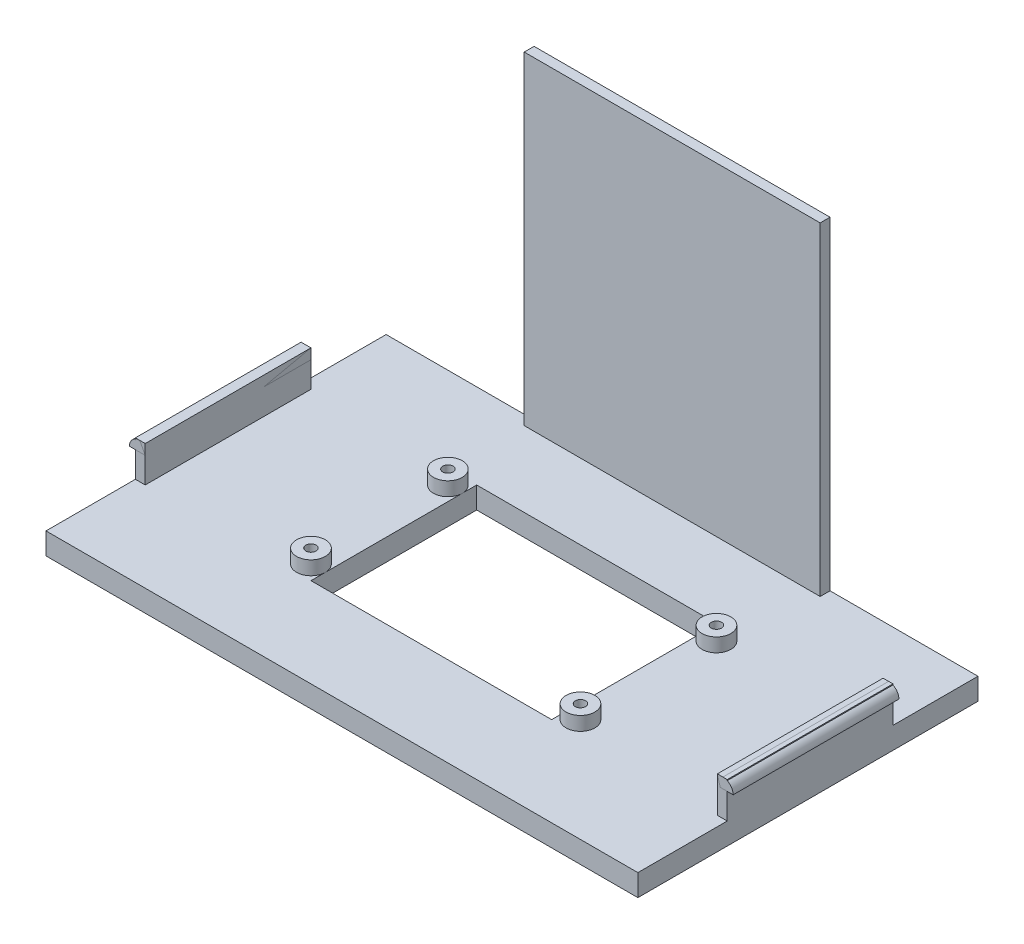
SolidWorks part; units mm, degrees
ref_plane "Plano frontal" through (0, 0, 0) normal (0, 0, 1) x (1, 0, 0)
ref_plane "Plano superior" through (0, 0, 0) normal (0, 1, 0) x (1, 0, 0)
ref_plane "Plano direito" through (0, 0, 0) normal (1, 0, 0) x (0, 0, -1)
sketch "Esboço1" plane through (0, 0, 0) normal (0, 1, 0) x (1, 0, 0)
  line L1 (0, 0) -> (150, 0)
  line L2 (0, 0) -> (0, 86.2)
  line L3 (0, 86.2) -> (150, 86.2)
  line L4 (150, 0) -> (150, 86.2)
  line L8 (75, 86.2) -> (75, 64.65) construction
  line L10 (44.5, 64.65) -> (105.5, 64.65)
  line L11 (44.5, 64.65) -> (44.5, 22.65)
  line L12 (44.5, 22.65) -> (105.5, 22.65)
  line L13 (105.5, 64.65) -> (105.5, 22.65)
  dimension "D1" = 86.2
  dimension "D2" = 42
  dimension "D3" = 61
  dimension "D4" = 150
extrude "Ressalto-extrusão1" add sketch "Esboço1" along normal blind 5.5
sketch "Esboço2" plane through (0, 0, 0) normal (0, 1, 0) x (1, 0, 0)
  line L0 (0, 43.1) -> (150, 43.1) construction
  line L1 (0, 86.2) -> (0, 0) construction
  line L2 (150, 0) -> (150, 86.2) construction
  line L3 (150, 43.1) -> (105.5, 64.65) construction
  line L4 (105.5, 64.65) -> (150, 64.65) construction
  line L5 (150, 64.65) -> (0, 64.65) construction
  line L6 (0, 64.65) -> (44.5, 22.65) construction
  line L7 (44.5, 22.65) -> (0, 22.65) construction
  line L8 (0, 22.65) -> (150, 22.65) construction
  line L10 (2.5, 22.65) -> (0, 22.65)
  line L11 (2.5, 22.65) -> (2.5, 64.65)
  line L12 (2.5, 64.65) -> (0, 64.65)
  line L13 (0, 22.65) -> (0, 64.65)
  line L14 (150, 22.65) -> (147.5, 22.65)
  line L15 (150, 22.65) -> (150, 64.65)
  line L16 (150, 64.65) -> (147.5, 64.65)
  line L17 (147.5, 22.65) -> (147.5, 64.65)
  dimension "D1" = 2.5
  dimension "D2" = 2.5
extrude "Ressalto-extrusão2" add sketch "Esboço2" along normal blind 14.6
sketch3d "3DSketch2"
  line L1 (147.5, 14.6, -22.65) -> (151.5, 14.6, -22.65)
  line L2 (147.5, 14.6, -22.65) -> (147.5, 14.6, -64.65)
  line L3 (147.5, 14.6, -64.65) -> (151.5, 14.6, -64.65)
  line L4 (151.5, 14.6, -22.65) -> (151.5, 14.6, -64.65)
  line L5 (2.5, 14.6, -22.65) -> (-1.5, 14.6, -22.65)
  line L6 (2.5, 14.6, -22.65) -> (2.5, 14.6, -64.65)
  line L7 (2.5, 14.6, -64.65) -> (-1.5, 14.6, -64.65)
  line L8 (-1.5, 14.6, -22.65) -> (-1.5, 14.6, -64.65)
  dimension "D1" = 4
  dimension "D2" = 4
extrude "Ressalto-extrusão3" add sketch "3DSketch2" along direction (0, -1, 0) on the side of the normal blind 2.6 separate body
fillet "Filete3" radius 2.6 1 edges
fillet "Filete4" radius 2.6 1 edges
sketch3d "3DSketch3"
  line L0 (44.5, 5.5, -22.65) -> (0, 5.5, -22.65) construction
  line L1 (0, 5.5, -22.65) -> (150, 5.5, -22.65) construction
  line L2 (150, 5.5, -22.65) -> (105.5, 5.5, -64.65) construction
  line L3 (105.5, 5.5, -22.65) -> (105.5, 5.5, -64.65) construction
  line L4 (105.5, 5.5, -64.65) -> (150, 5.5, -64.65) construction
  line L5 (150, 5.5, -64.65) -> (0, 5.5, -64.65) construction
  line L6 (112.8, 5.5, -22.65) -> (112.8, 5.5, -64.65) construction
  line L7 (37.2, 5.5, -64.65) -> (37.2, 5.5, -22.65) construction
  circle A0 centre (109.15, 5.5, -26.3) radius 3.65
  circle A1 centre (109.15, 5.5, -60.7648) radius 3.65
  circle A2 centre (40.85, 5.5, -26.3) radius 3.65
  circle A3 centre (109.15, 5.5, -26.3) radius 1.3
  circle A4 centre (40.85, 5.5, -26.3) radius 1.3
  circle A5 centre (109.15, 5.5, -60.7648) radius 1.3
  circle A6 centre (40.85, 5.5, -61) radius 3.65
  circle A7 centre (40.85, 5.5, -61) radius 1.3
  point P17 (105.5, 5.5, -22.65)
  point P22 (109.15, 1.85, -26.3)
  point P25 (109.15, 1.85, -60.7648)
  point P28 (40.85, 1.85, -26.3)
  point P29 (109.15, 4.2, -26.3)
  point P31 (40.85, 4.2, -26.3)
  point P33 (109.15, 4.2, -60.7648)
  point P37 (40.85, 1.85, -61)
  point P38 (40.85, 4.2, -61)
  dimension "D3" = 2.6
  dimension "D4" = 2.6
  dimension "D5" = 2.6
  dimension "D6" = 2.6
  dimension "D7" = 7.3
  dimension "D1" = 7.3
  dimension "D2" = 7.3
extrude "Ressalto-extrusão4" add sketch "3DSketch3" along direction (0, -1, 0) on the side of the normal blind 3.5
sketch3d "3DSketch4"
  line L0 (150, 5.5, -86.2) -> (0, 5.5, -86.2) construction
  line L1 (112.5, 5.5, -86.2) -> (37.5, 5.5, -86.2)
  line L2 (112.5, 5.5, -86.2) -> (112.5, 5.5, -83.7)
  line L3 (112.5, 5.5, -83.7) -> (37.5, 5.5, -83.7)
  line L4 (37.5, 5.5, -86.2) -> (37.5, 5.5, -83.7)
  point P6 (105.5, 5.5, -64.65)
  point P9 (0, 5.5, -86.2)
  dimension "D1" = 2.5
  dimension "D2" = 75
  dimension "D3" = 7
extrude "Ressalto-extrusão5" add sketch "3DSketch4" along direction (0, -1, 0) on the side against the normal blind 82
